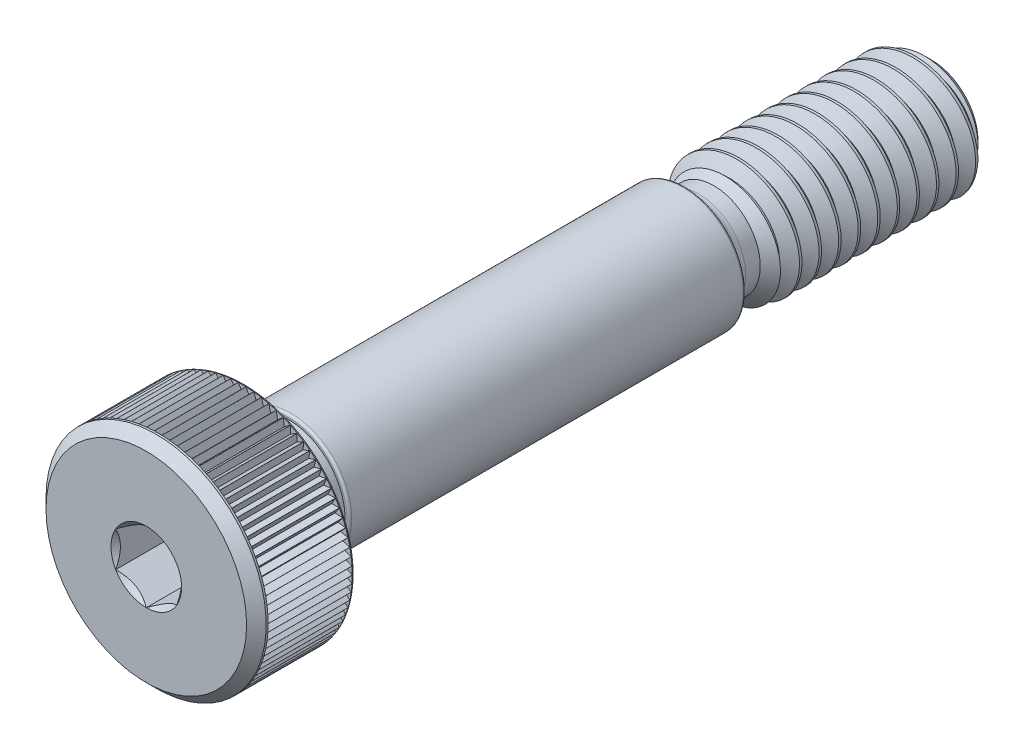
SolidWorks part; units mm, degrees
note: '?' marks a value the reader was unsure of.
other "DetailItem1"
other "DetailItem2"
other "DetailItem5"
other "DetailItem6"
ref_plane "Front" through (0, 0, 0) normal (0, 0, 1) x (1, 0, 0)
ref_plane "Top" through (0, 0, 0) normal (0, 1, 0) x (1, 0, 0)
ref_plane "Right" through (0, 0, 0) normal (1, 0, 0) x (0, 0, -1)
sketch "Sketch1" plane through (0, 0, 0) normal (1, 0, 0) x (0, 0, -1)
  line L7 (-16.05, 0) -> (16.05, 0) construction
  line L8 (16.05, 1.9) -> (15.45, 2.5)
  line L9 (16, 2.5866) -> (16.4, 1.8938) construction
  line L16 (16.4, 1.8938) -> (16.8, 2.5866) construction
  line L22 (16.05, 2.5) -> (16.05, 0)
  line L23 (-12.05, 4.5) -> (-12.05, 2.325)
  line L24 (-12.05, 2.325) -> (-10.25, 2.325)
  line L25 (16.8, 2.5866) -> (16, 2.5866) construction
  line L26 (6.55, 1.9) -> (7.15, 1.9)
  line L27 (7.15, 1.9) -> (7.75, 2.5)
  line L29 (-16.05, 4.5) -> (-16.05, 0)
  line L30 (-16.05, 4.5) -> (-12.05, 4.5)
  line L33 (-10.25, 2.5) -> (-10.25, 2.325)
  line L34 (-10.25, 2.5) -> (5.95, 2.5)
  line L35 (16.05, 2.5) -> (7.75, 2.5)
  line L37 (16.025, 2.5433) -> (16.775, 2.5433)
  line L38 (16.775, 2.5433) -> (16.45, 1.9804)
  line L39 (16.45, 1.9804) -> (16.35, 1.9804)
  line L40 (16.35, 1.9804) -> (16.025, 2.5433)
  line L41 (16.4, 1.9804) -> (16.4, 1.8938) construction
  line L42 (16.05, 2.5) -> (16.75, 2.5) construction
  line L47 (16.4, 2.5866) -> (16.4, 2.5) construction
  line L48 (5.95, 2.5) -> (6.55, 2.5) construction
  line L49 (-15.65, 4.5) -> (-16.05, 4.1)
  line L50 (16.05, -2.5) -> (7.75, -2.5)
  line L51 (-15.57, 4.5) -> (-15.57, 4.1) construction
  line L52 (-15.57, 4.1) -> (-12.13, 4.1) construction
  line L53 (-13.85, 4.1) -> (-13.85, 4.5) construction
  arc A0 (5.95, 2.5) -> (6.55, 1.9) centre (6.55, 2.5) ccw
  arc A1 (5.8572, 2.5) -> (5.9562, 2.4143) centre (5.8572, 2.4) cw
  arc A2 (-10.25, 2.4) -> (-10.15, 2.5) centre (-10.15, 2.4) cw
  arc A4 (-12.13, 4.5) -> (-12.05, 4.42) centre (-12.13, 4.42) cw
  point P2 (0, 0)
  point P20 (16.4, 2.5433)
  point P44 (-13.85, 4.5)
  point P45 (16.05, 2.5)
  point P46 (-15.57, 4.5)
  point P47 (-12.05, 3.4125)
  point P48 (7.15, 3.4125)
  point P51 (-14.05, 0)
  point P52 (14.45, 2.5)
  point P54 (16.05, 3.4125)
  point P57 (16.05, -3.4125)
  point P58 (7.15, -3.4125)
  dimension "D6" = 0.1
  dimension "D8" = 0.08
  dimension "D1" = 45
  dimension "Pitch" = 0.8
  dimension "D3" = 0.1
  dimension "D2" = 0.6
  dimension "D4" = 4.65
  dimension "D5" = 1.8
  dimension "D9" = 0.4
  dimension "D12" = 0.08
  dimension "D10" = 1.6
  dimension "D11" = 2
  dimension "Shoulder Diameter" = 5
  dimension "Thread Length" = 9.5
sketch "Sketch2" plane through (0, 0, 0) normal (0, 0, 1) x (1, 0, 0)
  line L9 (0, 1.4434) -> (-1.25, 0.7217)
  line L11 (-0.1571, 4.5) -> (0.1571, 4.5)
  line L12 (0.1571, 4.5) -> (0, 4.2278)
  line L13 (0, 4.2278) -> (-0.1571, 4.5)
  line L14 (0, 0) -> (-0.1571, 4.5) construction
  line L15 (0, 0) -> (0.1571, 4.5) construction
  line L16 (-1.25, 0.7217) -> (-1.25, -0.7217)
  line L17 (-1.25, -0.7217) -> (0, -1.4434)
  line L18 (0, -1.4434) -> (1.25, -0.7217)
  line L19 (1.25, -0.7217) -> (1.25, 0.7217)
  line L20 (1.25, 0.7217) -> (0, 1.4434)
  circle A0 centre (0, 0) radius 1.25 construction
  circle A2 centre (0, 0) radius 4.5
sketch "Sketch12" plane through (0, 0, 0) normal (1, 0, 0) x (0, 0, -1)
  line L0 (-16.05, 0) -> (-16.05, 4.1)
  line L1 (-16.05, 4.1) -> (-15.65, 4.5)
  line L2 (-15.65, 4.5) -> (-12.13, 4.5)
  line L3 (16.05, 1.9) -> (15.45, 2.5) construction
  line L5 (7.15, 1.9) -> (7.75, 2.5) construction
  line L7 (6.55, 1.9) -> (7.15, 1.9) construction
  line L8 (16.05, 1.9) -> (15.45, 2.5)
  line L9 (7.15, 1.9) -> (7.75, 2.5)
  line L11 (6.55, 1.9) -> (7.15, 1.9)
  line L12 (-12.05, 2.325) -> (-12.05, 4.42)
  line L13 (-12.05, 2.325) -> (-10.25, 2.325)
  line L14 (-10.25, 2.325) -> (-10.25, 2.4)
  line L15 (-10.15, 2.5) -> (5.8572, 2.5)
  line L16 (7.75, 2.5) -> (15.45, 2.5)
  line L17 (16.05, 1.9) -> (16.05, 0)
  line L18 (16.05, 0) -> (-16.05, 0)
  arc A0 (-12.05, 4.42) -> (-12.13, 4.5) centre (-12.13, 4.42) ccw construction
  arc A1 (-12.05, 4.42) -> (-12.13, 4.5) centre (-12.13, 4.42) ccw
  arc A5 (5.95, 2.5) -> (6.55, 1.9) centre (6.55, 2.5) ccw construction
  arc A6 (5.9562, 2.4143) -> (5.8572, 2.5) centre (5.8572, 2.4) ccw construction
  arc A7 (-10.15, 2.5) -> (-10.25, 2.4) centre (-10.15, 2.4) ccw construction
  arc A8 (5.9562, 2.4143) -> (6.55, 1.9) centre (6.55, 2.5) ccw
  arc A9 (5.9562, 2.4143) -> (5.8572, 2.5) centre (5.8572, 2.4) ccw
  arc A10 (-10.15, 2.5) -> (-10.25, 2.4) centre (-10.15, 2.4) ccw
revolve "Revolve1" add sketch "Sketch12" angle 360 mid plane about L18
sketch "Sketch8" plane through (0, 0, 16.05) normal (0, 0, 1) x (1, 0, 0)
  line L6 (0, -1.4434) -> (1.25, -0.7217) construction
  line L7 (-1.25, -0.7217) -> (0, -1.4434) construction
  line L8 (-1.25, 0.7217) -> (-1.25, -0.7217) construction
  line L9 (0, 1.4434) -> (-1.25, 0.7217) construction
  line L10 (1.25, 0.7217) -> (0, 1.4434) construction
  line L11 (1.25, -0.7217) -> (1.25, 0.7217) construction
  line L12 (0, -1.4434) -> (1.25, -0.7217)
  line L13 (-1.25, -0.7217) -> (0, -1.4434)
  line L14 (-1.25, 0.7217) -> (-1.25, -0.7217)
  line L15 (0, 1.4434) -> (-1.25, 0.7217)
  line L16 (1.25, 0.7217) -> (0, 1.4434)
  line L17 (1.25, -0.7217) -> (1.25, 0.7217)
extrude "Cut-Extrude2" cut sketch "Sketch8" against normal up to vertex (2 mm away) up to point (0, 0, 14.05)
sketch "Sketch9" plane through (0, 0, 16.05) normal (0, 0, 1) x (1, 0, 0)
  circle A1 centre (0, 0) radius 1.4434
extrude "Cut-Extrude4" cut sketch "Sketch9" against normal up to vertex (2 mm away) draft 45 up to point (0, 0, 14.05)
ref_axis "Center Axis1" through (0, 0, -14.7909) along (0, 0, 1)?
ref_plane "Contact Plane1" through (0, 0, -16.05) normal (0, 0, 1) x (1, 0, 0)
ref_plane "Contact Plane2" through (0, 0, 12.05) normal (0, 0, 1) x (1, 0, 0)
ref_plane "Plane2" through (0, 0, -7.15) normal (0, 0, -1) x (-1, 0, 0)
split "Split1" trim tools "Plane2" bodies to split 118 resulting bodies 122 123
sketch "Sketch3" plane through (0, 0, -16.05) normal (0, 0, 1) x (1, 0, 0)
  circle A0 centre (0, 0) radius 2.5 construction
  circle A2 centre (0, 0) radius 2.5
curve "Helix/Spiral1" pitch 0.8 height 9.5 turns 11.875
sketch "Sketch13" plane through (0, 0, 0) normal (1, 0, 0) x (0, 0, -1)
  line L0 (16.025, 2.5433) -> (16.775, 2.5433) construction
  line L1 (16.35, 1.9804) -> (16.025, 2.5433) construction
  line L2 (16.45, 1.9804) -> (16.35, 1.9804) construction
  line L3 (16.775, 2.5433) -> (16.45, 1.9804) construction
  line L16 (16.025, 2.5433) -> (16.775, 2.5433)
  line L17 (16.35, 1.9804) -> (16.025, 2.5433)
  line L18 (16.45, 1.9804) -> (16.35, 1.9804)
  line L19 (16.775, 2.5433) -> (16.45, 1.9804)
sweep "Cut-Sweep1" cut profiles "Sketch13" path "Helix/Spiral1" align with end faces yes
combine bodies "Combine1" operation type add bodies to combine 123 126
ref_plane "Plane1" through (0, 0, 15.57) normal (0, 0, 1) x (1, 0, 0)
sketch "Sketch11" plane through (0, 0, 15.57) normal (0, 0, 1) x (1, 0, 0)
  line L0 (0.1571, 4.5) -> (0, 4.2278) construction
  line L1 (0, 4.2278) -> (-0.1571, 4.5) construction
  line L2 (-0.1571, 4.5) -> (0.1571, 4.5) construction
  line L3 (0.1571, 4.5) -> (0, 4.2278)
  line L4 (0, 4.2278) -> (-0.1571, 4.5)
  line L5 (-0.1571, 4.5) -> (0.1571, 4.5)
  point P3 (0, 0.0018)
  point P8 (2.3908, 0.7309)
extrude "Cut-Extrude5" cut sketch "Sketch11" against normal up to vertex (3.44 mm away) up to point (0, 4.1, 12.13)
pattern_circular "CirPattern1" count 90 over 360 about axis through (0, 0, 0) along (0, 0, 1) of "Cut-Extrude5"
equation "\"D3@Sketch1\"=\"Pitch@Sketch1\"/8"
equation "\"D2@Sketch1\"=\"Pitch@Sketch1\"*.75"
equation "\"D4@Sketch1\"=\"Shoulder Diameter@Sketch1\"*.93"
equation "\"D5@Sketch1\"=\"Shoulder Length@Sketch1\"*.1"
equation "\"D6@Sketch1\"=\"Shoulder Diameter@Sketch1\"*.04*0.5"
equation "\"D8@Sketch1\"=\"Head Height@Sketch1\"*.02"
equation "\"D9@Sketch1\"=\"Head Height@Sketch1\"*.1"
equation "\"D4@Helix/Spiral1\"=\"Pitch@Sketch1\""
equation "\"D3@Helix/Spiral1\"=\"Thread Length@Sketch1\""
equation "\"D1@CirPattern1\" = 360 / \"Knurl Angle@Sketch2\""
equation "\"D12@Sketch1\"=\"Head Height@Sketch1\"*.02"
equation "\"D10@Sketch1\"=\"Pitch@Sketch1\"*2"
equation "\"D11@Sketch1\"=\"Head Height@Sketch1\"*0.5"
